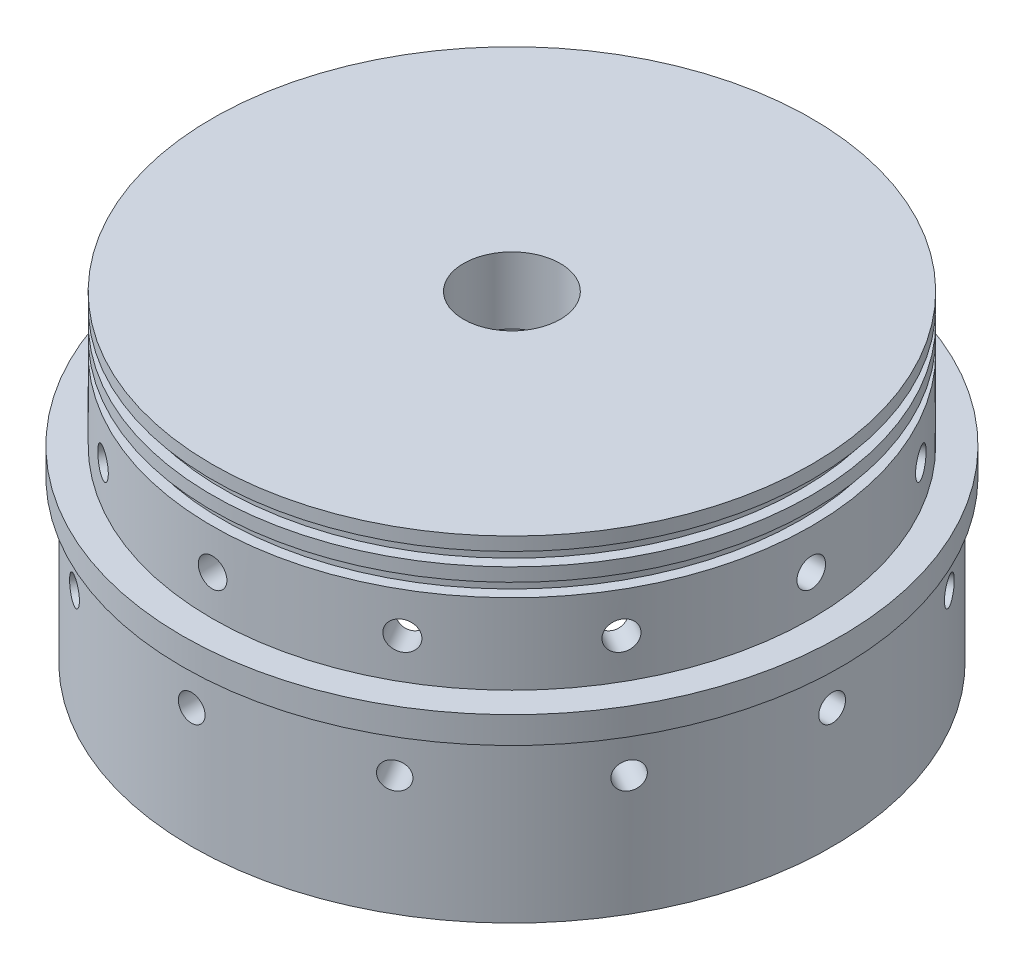
SolidWorks part; units mm, degrees
material "2024-T4"
ref_plane "Front Plane" through (0, 0, 0) normal (0, 0, 1) x (1, 0, 0)
ref_plane "Top Plane" through (0, 0, 0) normal (0, 1, 0) x (1, 0, 0)
ref_plane "Right Plane" through (0, 0, 0) normal (1, 0, 0) x (0, 0, -1)
sketch "Sketch1" plane through (0, 0, 0) normal (0, 1, 0) x (1, 0, 0)
  circle A0 centre (0, 0) radius 78.359
  dimension "D1" = 156.718
extrude "CenterRing(TotOD&Thk)" add sketch "Sketch1" along normal blind 6.35 contours A0 region at (0, 0, 0)
sketch "Sketch2" plane through (0, 6.35, 0) normal (0, 1, 0) x (1, 0, 0)
  circle A0 centre (0, 0) radius 71.247
  dimension "D1" = 142.494
extrude "TankRing(TankID&Ht)" add sketch "Sketch2" along normal blind 31.75
sketch "Sketch3" plane through (0, 0, 0) normal (0, -1, 0) x (1, 0, 0)
  circle A0 centre (0, 0) radius 76.2
  dimension "D1" = 152.4
extrude "FbrGlsRing(FbrGlsID&Ht)" add sketch "Sketch3" along normal blind 38.1
sketch "Sketch4" plane through (0, -38.1, 0) normal (0, -1, 0) x (1, 0, 0)
  circle A0 centre (0, 0) radius 65.0875
  circle A1 centre (0, 0) radius 76.2 construction
  circle A2 centre (0, 0) radius 76.2
  dimension "D1" = 130.175
extrude "Wall&BlkhdThk" cut sketch "Sketch4" against normal offset from surface (60.325 mm away) 15.875 contours A0 up to face at (0, 38.1, 71.247)
sketch "Sketch5" plane through (0, 0, 0) normal (0, 0, 1) x (1, 0, 0)
  line L0 (71.247, 38.1) -> (-71.247, 38.1) construction
  line L1 (-71.247, 38.1) -> (-71.247, 6.35) construction
  line L2 (-71.247, 38.1) -> (-71.247, 6.35)
  line L3 (71.247, 38.1) -> (-71.247, 38.1)
  line L4 (-71.247, 34.925) -> (-68.707, 34.925)
  line L5 (-68.707, 34.925) -> (-68.707, 31.75)
  line L6 (-68.707, 31.75) -> (-71.247, 31.75)
  line L7 (-71.247, 28.575) -> (-68.707, 28.575)
  line L8 (-68.707, 28.575) -> (-68.707, 25.4)
  line L9 (-68.707, 25.4) -> (-71.247, 25.4)
  line L10 (0, 6.35) -> (0, 38.1) construction
  line L11 (78.359, 6.35) -> (-78.359, 6.35) construction
  dimension "D1" = 2.54
  dimension "D2" = 3.175
  dimension "D3" = 3.175
  dimension "D4" = 3.175
  dimension "D5" = 3.175
revolve "O-Ring Channel" cut sketch "Sketch5" angle 360 about L10 region at (-69.977, 33.3375, 0) region at (-69.977, 26.9875, 0)
sketch "Sketch6" plane through (0, 0, 0) normal (0, 0, 1) x (1, 0, 0)
  line L0 (78.359, 6.35) -> (-78.359, 6.35) construction
  line L1 (78.359, 6.35) -> (-78.359, 6.35)
  circle A0 centre (0, 15.875) radius 3.4
  dimension "D1" = 6.8
  dimension "D2" = 9.525
extrude "TankBoltHole" cut sketch "Sketch6" against normal through all contours A0 region at (0, 15.875, 0)
pattern_circular "TankBoltCount" count 12 over 360 about axis through (0, 38.1, 0) along (0, -1, 0) of "TankBoltHole"
sketch "Sketch7" plane through (0, 0, 0) normal (0, 0, 1) x (1, 0, 0)
  line L0 (-76.2, 0) -> (76.2, 0) construction
  line L1 (-76.2, 0) -> (76.2, 0)
  circle A0 centre (0, -9.525) radius 3.175
  dimension "D1" = 6.35
  dimension "D2" = 9.525
extrude "FbrGlsBoltHole" cut sketch "Sketch7" against normal through all contours A0 region at (0, -9.525, 0)
pattern_circular "FbrGlsBoltCount" count 12 over 360 about axis through (0, -38.1, 0) along (0, 1, 0) of "FbrGlsBoltHole" reverse direction yes
sketch "Sketch8" plane through (0, 38.1, 0) normal (0, 1, 0) x (1, 0, 0)
  circle A0 centre (0, 0) radius 11.5094
  dimension "D1" = 23.0188
extrude "3/4NPTFemDrill" cut sketch "Sketch8" against normal through all
fillet "Smoothing" radius 12.7 1 edges at (0, 22.225, 65.0875)
sketch "Sketch9" plane through (0, -38.1, 0) normal (0, -1, 0) x (1, 0, 0)
  circle A0 centre (0, 0) radius 71.4375
  circle A1 centre (0, 0) radius 76.2 construction
  circle A2 centre (0, 0) radius 76.2
  dimension "D1" = 4.7625
extrude "FbrGlsRingTrim" cut sketch "Sketch9" against normal blind 19.05 contours A0
equation "\"D4@Sketch5\"=\"D2@Sketch5\""
equation "\"D5@Sketch5\"=\"D3@Sketch5\""
